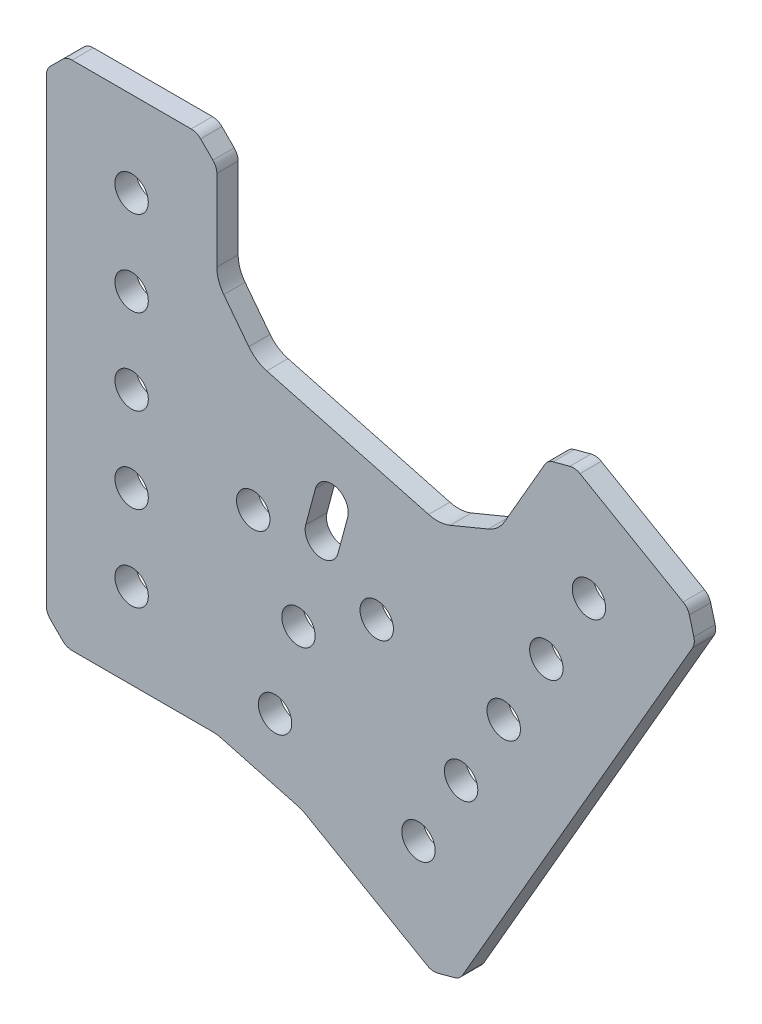
SolidWorks part; units mm, degrees
material "1060 Alloy"
ref_plane "Front Plane" through (0, 0, 0) normal (0, 0, 1) x (1, 0, 0)
ref_plane "Top Plane" through (0, 0, 0) normal (0, 1, 0) x (1, 0, 0)
ref_plane "Right Plane" through (0, 0, 0) normal (1, 0, 0) x (0, 0, -1)
ref_plane "Plane1" through (0, 0, 0) normal (0, 0, -1) x (-1, 0, 0)
sketch "Sketch1" plane through (0, 0, 0) normal (0, 0, -1) x (-1, 0, 0)
  line L0 (-43.4514, 32.3513) -> (-44.8955, 37.7408)
  line L1 (-40.0868, 39.0293) -> (-38.6427, 33.6398)
  line L2 (-2.4142, 0.5858) -> (-0.5858, 2.4142)
  line L3 (0, 3.8284) -> (0, 72.3716)
  line L4 (-0.5858, 73.7858) -> (-2.4142, 75.6142)
  line L5 (-3.8284, 76.2) -> (-21.5716, 76.2)
  line L6 (-22.9858, 75.6142) -> (-24.8142, 73.7858)
  line L7 (-25.4, 72.3716) -> (-25.4, 60.2893)
  line L8 (-26.4332, 57.2455) -> (-30.1623, 52.3857)
  line L9 (-32.835, 50.5998) -> (-56.961, 44.1353)
  line L10 (-60.1685, 44.3455) -> (-65.8279, 46.6897)
  line L11 (-68.2447, 48.8091) -> (-74.2858, 59.2727)
  line L12 (-75.5002, 60.2045) -> (-77.9979, 60.8738)
  line L13 (-79.5155, 60.674) -> (-94.8815, 51.8024)
  line L14 (-95.8134, 50.588) -> (-96.4826, 48.0903)
  line L15 (-96.2828, 46.5727) -> (-62.0113, -12.7874)
  line L16 (-60.7968, -13.7193) -> (-58.2992, -14.3885)
  line L17 (-56.7815, -14.1887) -> (-38.6701, -3.7321)
  line L18 (-37.4642, -3.2326) -> (-26.0358, -0.1704)
  line L19 (-24.7417, 0) -> (-3.8284, 0)
  circle A0 centre (-12.7, 25.4) radius 2.4892
  circle A1 centre (-61.7985, 12.2441) radius 2.4892
  circle A2 centre (-74.4985, 34.2411) radius 2.4892
  circle A3 centre (-12.7, 50.8) radius 2.4892
  circle A4 centre (-80.8485, 45.2397) radius 2.4892
  circle A5 centre (-68.1485, 23.2426) radius 2.4892
  circle A6 centre (-55.4485, 1.2456) radius 2.4892
  circle A7 centre (-12.7, 63.5) radius 2.4892
  circle A8 centre (-12.7, 38.1) radius 2.4892
  circle A9 centre (-12.7, 12.7) radius 2.4892
  circle A10 centre (-30.8255, 31.6499) radius 2.4892
  circle A11 centre (-49.2263, 26.7194) radius 2.4892
  circle A12 centre (-37.5607, 19.9842) radius 2.4892
  circle A13 centre (-34.0743, 6.9728) radius 2.4892
  arc A14 (-44.8955, 37.7408) -> (-40.0868, 39.0293) centre (-42.4912, 38.3851) cw
  arc A15 (-38.6427, 33.6398) -> (-43.4514, 32.3513) centre (-41.047, 32.9956) cw
  arc A16 (-0.5858, 2.4142) -> (0, 3.8284) centre (-2, 3.8284) ccw
  arc A17 (0, 72.3716) -> (-0.5858, 73.7858) centre (-2, 72.3716) ccw
  arc A18 (-2.4142, 75.6142) -> (-3.8284, 76.2) centre (-3.8284, 74.2) ccw
  arc A19 (-21.5716, 76.2) -> (-22.9858, 75.6142) centre (-21.5716, 74.2) ccw
  arc A20 (-24.8142, 73.7858) -> (-25.4, 72.3716) centre (-23.4, 72.3716) ccw
  arc A21 (-25.4, 60.2893) -> (-26.4332, 57.2455) centre (-30.4, 60.2893) cw
  arc A22 (-30.1623, 52.3857) -> (-32.835, 50.5998) centre (-34.1291, 55.4295) cw
  arc A23 (-56.961, 44.1353) -> (-60.1685, 44.3455) centre (-58.2551, 48.9649) cw
  arc A24 (-65.8279, 46.6897) -> (-68.2447, 48.8091) centre (-63.9145, 51.3091) cw
  arc A25 (-74.2858, 59.2727) -> (-75.5002, 60.2045) centre (-76.0178, 58.2727) ccw
  arc A26 (-77.9979, 60.8738) -> (-79.5155, 60.674) centre (-78.5155, 58.9419) ccw
  arc A27 (-94.8815, 51.8024) -> (-95.8134, 50.588) centre (-93.8815, 50.0703) ccw
  arc A28 (-96.4826, 48.0903) -> (-96.2828, 46.5727) centre (-94.5508, 47.5727) ccw
  arc A29 (-62.0113, -12.7874) -> (-60.7968, -13.7193) centre (-60.2792, -11.7874) ccw
  arc A30 (-58.2992, -14.3885) -> (-56.7815, -14.1887) centre (-57.7815, -12.4567) ccw
  arc A31 (-38.6701, -3.7321) -> (-37.4642, -3.2326) centre (-36.1701, -8.0622) cw
  arc A32 (-26.0358, -0.1704) -> (-24.7417, 0) centre (-24.7417, -5) cw
  arc A33 (-3.8284, 0) -> (-2.4142, 0.5858) centre (-3.8284, 2) ccw
extrude "Boss-Extrude1" add sketch "Sketch1" against normal blind 3.175
